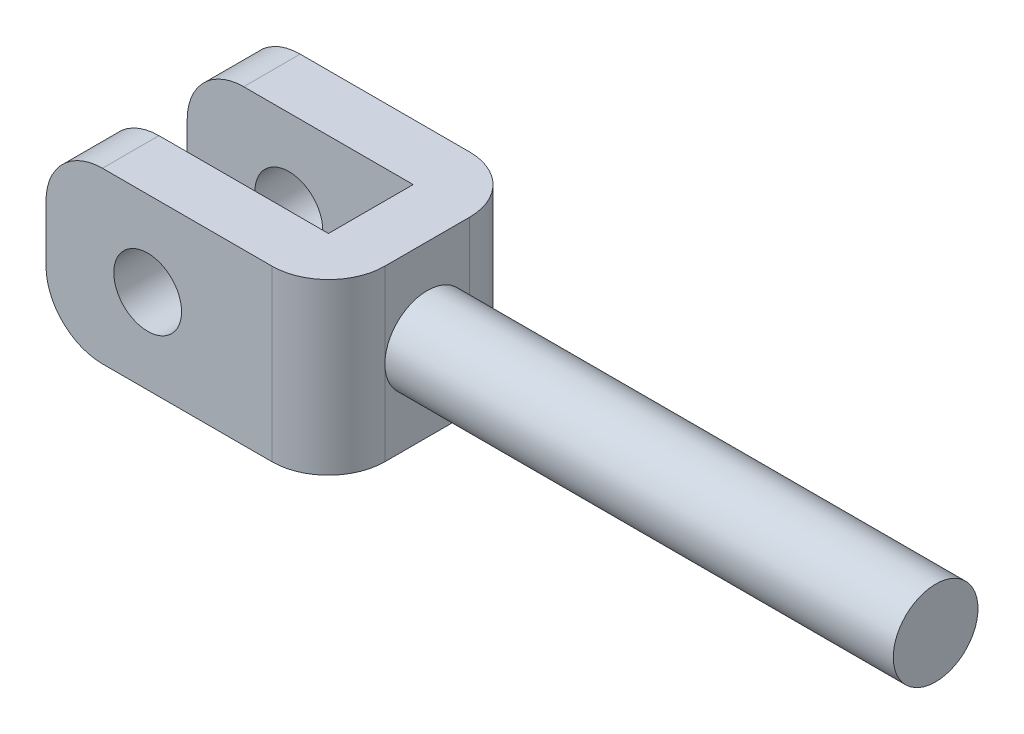
SolidWorks part; units mm, degrees
ref_plane "Front Plane" through (0, 0, 0) normal (0, 0, 1) x (1, 0, 0)
ref_plane "Top Plane" through (0, 0, 0) normal (0, 1, 0) x (1, 0, 0)
ref_plane "Right Plane" through (0, 0, 0) normal (1, 0, 0) x (0, 0, -1)
sketch "Sketch1" plane through (0, 0, 0) normal (1, 0, 0) x (0, 0, -1)
  circle A0 centre (0, 0) radius 0.75
  dimension "D1" = 1.5
extrude "Boss-Extrude1" add sketch "Sketch1" along normal blind 10
sketch "Sketch2" plane through (0, 0, 0) normal (0, 1, 0) x (1, 0, 0)
  line L0 (1, 1.75) -> (1, -1.75)
  line L2 (0, 0.75) -> (0, -0.75)
  line L5 (1, -1.75) -> (-4, -1.75)
  line L6 (-4, 1.75) -> (-4, 0.75)
  line L7 (1, 1.75) -> (-4, 1.75)
  line L8 (0, 0.75) -> (-4, 0.75)
  line L10 (-4, -0.75) -> (0, -0.75)
  line L11 (-4, -0.75) -> (-4, -1.75)
  line L13 (-4, 1.75) -> (-4, -1.75) construction
  line L14 (-3, 0.75) -> (-3, -0.75) construction
  line L15 (0, 0.75) -> (-3, 0.75) construction
  line L16 (0, -0.75) -> (-3, -0.75) construction
  dimension "D2" = 1
extrude "Boss-Extrude2" add sketch "Sketch2" along normal blind 1.5 and the other way blind 1.5
fillet "Fillet1" radius 1 6 edges at (-4, 1.5, -1.25) (-4, -1.5, -1.25) (-4, -1.5, 1.25) (-4, 1.5, 1.25) (1, 0, -1.75) (1, 0, 1.75)
sketch "Sketch3" plane through (0, 0, -1.75) normal (0, 0, -1) x (-1, 0, 0)
  line L0 (0, -1.5) -> (3, -1.5) construction
  line L2 (0, 1.5) -> (0, -1.5) construction
  circle A0 centre (2.2, 0) radius 0.6
  dimension "D1" = 1.2
  dimension "D2" = 1.5
  dimension "D3" = 2.2
extrude "Cut-Extrude1" cut sketch "Sketch3" against normal blind 5
